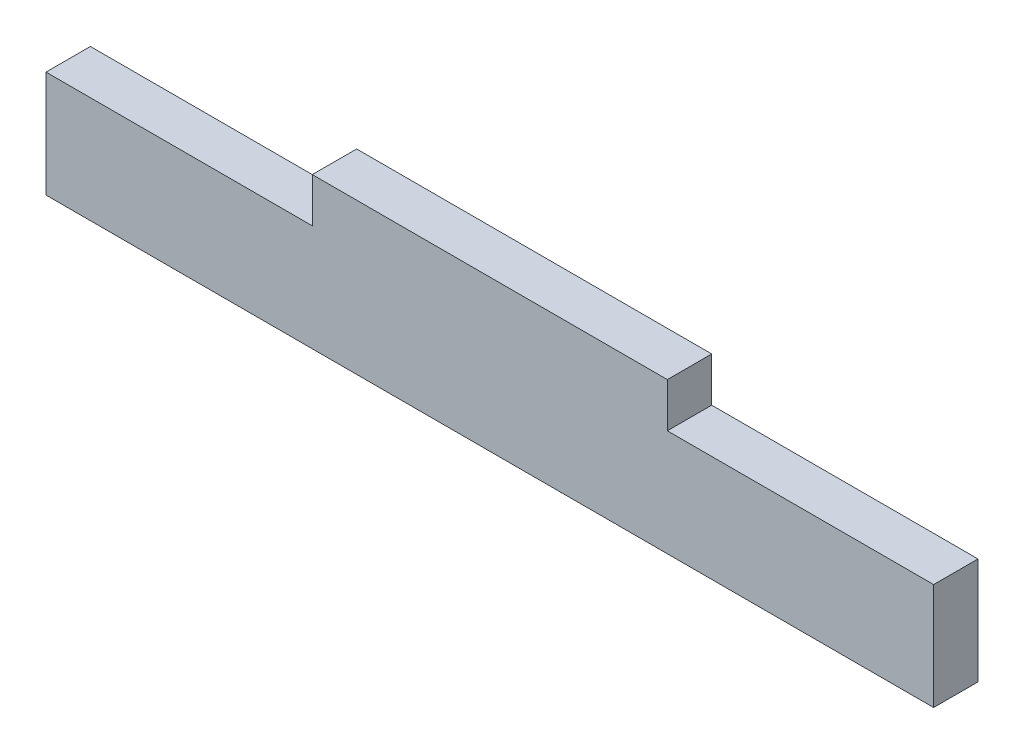
SolidWorks part; units mm, degrees
ref_plane "Front" through (0, 0, 0) normal (0, 0, 1) x (1, 0, 0)
ref_plane "Top" through (0, 0, 0) normal (0, 1, 0) x (1, 0, 0)
ref_plane "Right" through (0, 0, 0) normal (1, 0, 0) x (0, 0, -1)
sketch "Skizze1" plane through (0, 0, 0) normal (0, 0, 1) x (1, 0, 0)
  line L0 (0, 0) -> (0, 17) construction
  line L1 (20, 17) -> (-20, 17)
  line L2 (-20, 17) -> (-20, 12)
  line L3 (-20, 12) -> (-50, 12)
  line L4 (-50, 12) -> (-50, 0)
  line L5 (-50, 0) -> (50, 0)
  line L6 (50, 12) -> (50, 0)
  line L7 (20, 12) -> (50, 12)
  line L8 (20, 17) -> (20, 12)
  dimension "D1" = 5
  dimension "D2" = 12
  dimension "D3" = 40
  dimension "D4" = 100
extrude "Aufsatz-Linear austragen1" add sketch "Skizze1" along normal blind 5
